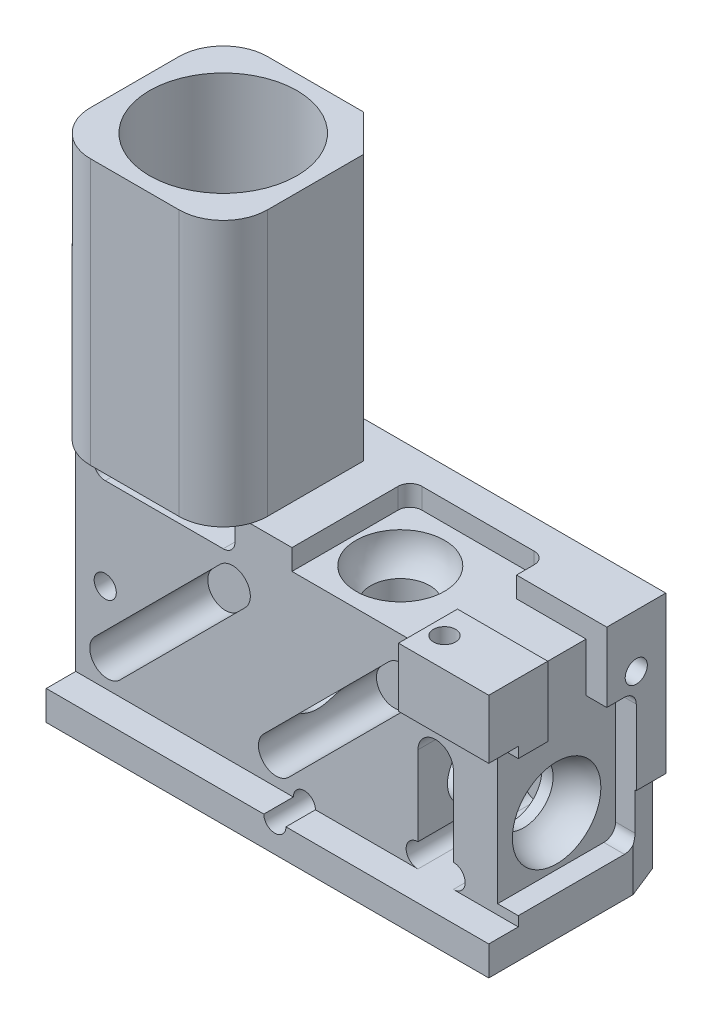
SolidWorks part; units mm, degrees
ref_plane "Front Plane" through (0, 0, 0) normal (0, 0, 1) x (1, 0, 0)
ref_plane "Top Plane" through (0, 0, 0) normal (0, 1, 0) x (1, 0, 0)
ref_plane "Right Plane" through (0, 0, 0) normal (1, 0, 0) x (0, 0, -1)
sketch "Sketch1" plane through (0, 0, 0) normal (0, 1, 0) x (1, 0, 0)
  line L1 (7.5, 3) -> (-7.5, 3)
  line L2 (7.5, 3) -> (7.5, -3)
  line L3 (7.5, -3) -> (-7.5, -3)
  line L4 (-7.5, 3) -> (-7.5, -3)
  line L5 (7.5, 3) -> (-7.5, -3) construction
  line L6 (7.5, -3) -> (-7.5, 3) construction
  point P0 (0, 0)
  dimension "D1" = 6
  dimension "D2" = 15
extrude "Main Body Ext" add sketch "Sketch1" along normal blind 8.3
sketch "Sketch8" plane through (0, 8.3, 0) normal (0, 1, 0) x (1, 0, 0)
  line L0 (-2.75, 3) -> (-1.5, 1.75)
  line L1 (-2.75, 3) -> (-7.5, 3)
  line L2 (-1.5, 1.75) -> (-1.5, -3)
  line L3 (-1.5, -3) -> (-7.5, -3)
  line L4 (-7.5, 3) -> (-7.5, -3)
  line L5 (-2.125, 2.375) -> (-7.5, -3) construction
  line L6 (-1.5, -3) -> (-7.5, 3) construction
  line L7 (-7.5, 3) -> (-7.5, -3) construction
  line L8 (0, 0) -> (-4.5, 0) construction
  point P0 (-4.5, 0)
  dimension "D1" = 6
  dimension "D2" = 6
  dimension "D3" = 1.25
  dimension "D4" = 3
extrude "Emission Path Ext" add sketch "Sketch8" along normal blind 9
sketch "Sketch3" plane through (0, 0, 0) normal (0, -1, 0) x (1, 0, 0)
  line L0 (-7.5, -3) -> (-7.5, 3) construction
  line L1 (0, 0) -> (-4.5, 0) construction
  circle A0 centre (-4.5, 0) radius 1.25
  dimension "D1" = 3
  dimension "D2" = 2.5
extrude "Emission and Grin Cut" cut sketch "Sketch3" against normal through all
sketch "Sketch4" plane through (7.5, 0, 0) normal (1, 0, 0) x (0, 0, -1)
  line L1 (-3, 0) -> (3, 0) construction
  circle A0 centre (0, 3) radius 1
  dimension "D1" = 2
  dimension "D2" = 3
extrude "Drum Lens Cut" cut sketch "Sketch4" against normal offset from surface (13 mm away) 2 up to face at (-7.5, 8.65, 0)
sketch "Sketch41" plane through (0, 8.3, 0) normal (0, 1, 0) x (1, 0, 0)
  line L1 (7.5, 3) -> (-2.75, 3) construction
  line L2 (-1.5, -3) -> (-1.5, 1.75) construction
  circle A0 centre (1.5, 0) radius 1
  dimension "D1" = 2
  dimension "D2" = 3
  dimension "D3" = 3
extrude "Addtl Light Source" cut sketch "Sketch41" against normal blind 5
sketch "Sketch5" plane through (0, 0, 3) normal (0, 0, 1) x (1, 0, 0)
  line L0 (-7.5, 0) -> (7.5, 0) construction
  line L1 (7.5, 8.3) -> (-7.5, 8.3)
  line L2 (7.5, 8.3) -> (7.5, 1)
  line L3 (7.5, 1) -> (-7.5, 1)
  line L4 (-7.5, 8.3) -> (-7.5, 1)
  line L5 (7.5, 8.3) -> (-7.5, 1) construction
  line L6 (7.5, 1) -> (-7.5, 8.3) construction
  line L7 (-1.5, 8.3) -> (7.5, 8.3) construction
  line L9 (7.5, 8.3) -> (7.5, 0) construction
  line L10 (-7.5, 17.3) -> (-7.5, 0) construction
  point P0 (0, 4.65)
  dimension "D1" = 1
extrude "FilterCover Cut1" cut sketch "Sketch5" against normal blind 1
sketch "Top-LED-Screw" plane through (0, 0, 2) normal (0, 0, 1) x (1, 0, 0)
  line L1 (7.5, 8.3) -> (4.44, 8.3)
  line L2 (7.5, 8.3) -> (7.5, 6.3)
  line L3 (7.5, 6.3) -> (4.44, 6.3)
  line L4 (4.44, 8.3) -> (4.44, 6.3)
  dimension "D1" = 2
  dimension "D2" = 3.06
extrude "Boss-Extrude1" add sketch "Top-LED-Screw" along normal blind 1
sketch "Sketch6" plane through (0, 0, 2) normal (0, 0, 1) x (1, 0, 0)
  line L0 (5.3, 4.5) -> (5.3, 1.8)
  line L1 (4.1, 4.5) -> (5.3, 4.5) construction
  line L2 (5.3, 1) -> (4.1, 1)
  line L3 (-7.5, 1) -> (7.5, 1) construction
  line L4 (-7.5, 8.3) -> (-7.5, 1) construction
  line L5 (-6.9, 7.9) -> (-6.9, 7.5)
  line L6 (4.1, 4.5) -> (4.1, 1.8)
  line L7 (-1.5, 8.3) -> (-7.5, 8.3) construction
  line L8 (-2.1, 7.9) -> (-2.1, 7.5)
  line L9 (-6, 1.5) -> (-6, 1) construction
  line L10 (-2.5, 8.3) -> (-6.5, 8.3)
  line L11 (-4.5, 3) -> (-4.5, 1) construction
  line L12 (-4.5, 3) -> (0.4851, 3) construction
  line L13 (-2.5, 7.1) -> (-6.5, 7.1)
  line L14 (-0.282, 1.5) -> (-0.282, 1) construction
  line L15 (-2.5, 8.3) -> (-6.5, 7.1) construction
  line L16 (-2.5, 7.1) -> (-6.5, 8.3) construction
  line L17 (4.1, 1.8) -> (5.3, 1.8) construction
  line L18 (-2.6059, 6.5912) -> (-6.8485, 2.3485)
  line L19 (7.5, 1) -> (7.5, 6.3) construction
  line L20 (-1.7574, 5.7426) -> (-6, 1.5)
  line L21 (-2.6059, 6.5912) -> (-6, 1.5) construction
  line L22 (-6.8485, 2.3485) -> (-1.7574, 5.7426) construction
  line L23 (1.826, 3.6081) -> (1.826, 1.6081) construction
  line L24 (1.826, 3.6081) -> (3.2165, 3.6081) construction
  line L25 (3.1121, 6.5912) -> (-1.1305, 2.3485)
  line L26 (3.9606, 5.7426) -> (-0.282, 1.5)
  line L27 (3.1121, 6.5912) -> (-0.282, 1.5) construction
  line L28 (-1.1305, 2.3485) -> (3.9606, 5.7426) construction
  line L33 (-2.5, 8.3) -> (1.102, 8.3) construction
  line L34 (1.102, 8.3) -> (1.102, 7.1) construction
  line L35 (1.102, 7.1) -> (-2.5, 7.1) construction
  line L36 (-6.5, 7.1) -> (-4.098, 7.1) construction
  line L37 (-4.098, 7.1) -> (-4.098, 8.3) construction
  line L38 (-4.098, 8.3) -> (-6.5, 8.3) construction
  line L39 (-6.5, 8.3) -> (-2.7284, 6.992) construction
  arc A0 (-2.5, 8.3) -> (-2.1, 7.9) centre (-2.5, 7.9) cw
  arc A1 (4.1, 4.5) -> (5.3, 4.5) centre (4.7, 4.5) cw
  arc A2 (-6.5, 8.3) -> (-6.9, 7.9) centre (-6.5, 7.9) ccw
  arc A3 (-2.6059, 6.5912) -> (-1.7574, 5.7426) centre (-2.1816, 6.1669) cw
  arc A4 (4.1, 1) -> (4.1, 1.8) centre (4.1, 1.4) cw
  arc A5 (-6.8485, 2.3485) -> (-6, 1.5) centre (-6.4243, 1.9243) ccw
  arc A6 (5.3, 1) -> (5.3, 1.8) centre (5.3, 1.4) ccw
  arc A7 (-6.5, 7.1) -> (-6.9, 7.5) centre (-6.5, 7.5) cw
  arc A8 (-2.5, 7.1) -> (-2.1, 7.5) centre (-2.5, 7.5) ccw
  arc A9 (3.1121, 6.5912) -> (3.9606, 5.7426) centre (3.5364, 6.1669) cw
  arc A10 (-1.1305, 2.3485) -> (-0.282, 1.5) centre (-0.7063, 1.9243) ccw
  point P5 (-4.5, 7.7)
  point P10 (-4.3029, 4.0456)
  point P21 (1.415, 4.0456)
  dimension "D10" = 0.5
  dimension "D5" = 2.2
  dimension "D8" = 0.4
  dimension "D11" = 0.4
  dimension "D12" = 0.4
  dimension "D1" = 1.2
  dimension "D2" = 45
  dimension "D3" = 3.5
  dimension "D4" = 1.2
  dimension "D6" = 2
  dimension "D7" = 4
  dimension "D9" = 3
  dimension "D13" = 1.2
  dimension "D14" = 3
  dimension "D15" = 6
  dimension "D16" = 45
  dimension "D17" = 0.5
  dimension "D18" = 1.2
  dimension "D19" = 2
  dimension "D20" = 6
extrude "FilterSet Cut2" cut sketch "Sketch6" against normal offset from surface (4 mm away) 1 up to face at (-0.0625, 9.2833, -3)
sketch "Sketch10" plane through (0, 17.3, 0) normal (0, 1, 0) x (1, 0, 0)
  line L0 (-4.5, 0) -> (-4.5, -3) construction
  line L1 (-7.5, -3) -> (-1.5, -3) construction
  line L3 (-4.5, 0) -> (-7.5, 0) construction
  line L4 (-7.5, 3) -> (-7.5, -3) construction
  circle A0 centre (-4.5, 0) radius 2.5
  dimension "D1" = 5
extrude "Emission Lens Cut" cut sketch "Sketch10" against normal offset from surface (8.5 mm away) 0.5 up to face at (-4.125, 8.3, 1.3125)
sketch "Sketch12" plane through (7.5, 0, 0) normal (1, 0, 0) x (0, 0, -1)
  line L0 (0, 3.635) -> (0, 0) construction
  line L1 (1.6, 5.94) -> (-1.6, 5.94)
  line L2 (1.6, 5.94) -> (1.6, 1.33) construction
  line L3 (-2, 1.33) -> (1.6, 1.33)
  line L4 (-1.6, 5.94) -> (-1.6, 1.33) construction
  line L5 (1.6, 5.94) -> (-1.6, 1.33) construction
  line L6 (1.6, 1.33) -> (-1.6, 5.94) construction
  line L7 (-3, 0) -> (3, 0) construction
  line L9 (-1.6, 5.94) -> (-2, 5.94)
  line L10 (-2, 1) -> (-2, 6.3) construction
  line L11 (-2, 5.94) -> (-2, 1.33)
  line L12 (2, 5.54) -> (2, 1.73)
  arc A1 (1.6, 5.94) -> (2, 5.54) centre (1.6, 5.54) cw
  arc A2 (1.6, 1.33) -> (2, 1.73) centre (1.6, 1.73) ccw
  circle A3 centre (0, 3) radius 1 construction
  point P0 (0, 3.635)
  dimension "D2" = 4.61
  dimension "D3" = 1.67
  dimension "D1" = 3.2
  dimension "D4" = 0.4
sketch "Sketch15" plane through (0, 0, 0) normal (0, -1, 0) x (1, 0, 0)
  line L0 (-6.25, 1.875) -> (-6.25, -1.875) construction
  line L2 (-1.5, 0) -> (-4.5, 0) construction
  line L3 (-4.5, 0) -> (-6.25, 0) construction
  circle A0 centre (-6.25, -1.875) radius 0.795
  circle A1 centre (-6.25, 1.875) radius 0.795
  circle A2 centre (-1.5, 0) radius 0.795
  dimension "D4" = 1.59
  dimension "D1" = 3.75
  dimension "D2" = 3
  dimension "D3" = 1.75
extrude "Magnets Cut" cut sketch "Sketch15" against normal blind 0.9
sketch "Sketch18" plane through (0, 0, 2) normal (0, 0, 1) x (1, 0, 0)
  line L0 (-7.5, 8.3) -> (-7.5, 1) construction
  line L1 (7.5, 1) -> (7.5, 6.3) construction
  line L2 (4.44, 8.3) -> (-1.5, 8.3) construction
  line L3 (-7.5, 0) -> (7.5, 0) construction
  line L7 (-7.5, 1) -> (4.1, 1) construction
  line L9 (-7.5, 1) -> (-7.5, 0) construction
  circle A0 centre (-6.5, 4) radius 0.375
  circle A1 centre (6, 5.8) radius 0.375
  circle A2 centre (0.25, 1) radius 0.375
  dimension "D1" = 0.75
  dimension "D2" = 1
  dimension "D3" = 2.5
  dimension "D4" = 1.5
  dimension "D5" = 3
  dimension "D6" = 1
  dimension "D7" = 7.75
extrude "Screw Holes Cut" cut sketch "Sketch18" against normal blind 2.5 and the other way through all
fillet "External Fillet 1" radius 1.5 2 edges at (-7.5, 8.65, -3)
sketch "Sketch14" plane through (0, 0, 0) normal (0, -1, 0) x (1, 0, 0)
  line L0 (7.5, -3) -> (7.5, -1.8916)
  line L1 (7.5, 3) -> (7.5, -3) construction
  line L2 (7.5, -1.8916) -> (7.0566, -3)
  line L3 (7.5, -3) -> (-6, -3) construction
  line L4 (7.0566, -3) -> (7.5, -3)
  line L5 (7.5, -3) -> (-7.5, 3) construction
  line L6 (-7.5, -1.5) -> (-7.5, 3) construction
  line L7 (-7.5, 3) -> (7.5, 3) construction
  dimension "D1" = 1.1938
sketch "Sketch28" plane through (0, 7.1, 0) normal (0, 1, 0) x (1, 0, 0)
  circle A0 centre (-4.5, 0) radius 1.5
  dimension "D1" = 3
extrude "Vertical-Path-Cut" cut sketch "Sketch28" against normal blind 4 and the other way through all
extrude "Set-Screw-Notch" cut sketch "Sketch14" against normal blind 3
extrude "Cut-Extrude Original Light" cut sketch "Sketch12" against normal blind 0.7
sketch "Sketch44" plane through (0, 8.3, 0) normal (0, 1, 0) x (1, 0, 0)
  line L0 (-0.17, -2) -> (4.44, -2)
  line L1 (-0.17, -2) -> (-0.17, 1.6)
  line L2 (4.44, -2) -> (4.44, 1.6)
  line L3 (0.23, 2) -> (4.04, 2)
  line L6 (4.44, -2) -> (-1.5858, -2) construction
  circle A0 centre (1.5, 0) radius 1 construction
  arc A1 (4.44, 1.6) -> (4.04, 2) centre (4.04, 1.6) ccw
  arc A2 (-0.17, 1.6) -> (0.23, 2) centre (0.23, 1.6) cw
  point P10 (4.44, 2)
  point P13 (-0.17, 2)
  dimension "D3" = 1.67
  dimension "D4" = 0.4
  dimension "D5" = 0.4
  dimension "D1" = 4
  dimension "D2" = 4.61
extrude "Cut-Extrude Addtl Light" cut sketch "Sketch44" against normal blind 0.7
sketch "Sketch29" plane through (7.5, 0, 0) normal (1, 0, 0) x (0, 0, -1)
  line L0 (3, 8.3) -> (3, 3) construction
  line L1 (-3, 8.3) -> (3, 8.3) construction
  circle A0 centre (2, 6.5) radius 0.375
  circle A1 centre (0, 3) radius 1 construction
  dimension "D1" = 0.75
  dimension "D2" = 1
  dimension "D3" = 1.8
  dimension "D5" = 3.5
  dimension "D6" = 2
extrude "Side-LED-Screw" cut sketch "Sketch29" against normal blind 2.5
sketch "Sketch31" plane through (6.8, 0, 0) normal (1, 0, 0) x (0, 0, -1)
  circle A0 centre (0, 3) radius 1.6
  dimension "D1" = 3.2
sketch "Sketch32" plane through (7.5, 0, 0) normal (1, 0, 0) x (0, 0, -1)
  line L0 (-3, 8.3) -> (3, 8.3) construction
  line L1 (-1, 8.3) -> (1, 8.3)
  line L2 (-1, 8.3) -> (-1, 5.94)
  line L3 (-1, 5.94) -> (1, 5.94)
  line L4 (1, 8.3) -> (1, 5.94)
  line L5 (1.6, 5.94) -> (-2, 5.94) construction
  line L6 (-2, 5.94) -> (-2, 6.3) construction
  line L8 (3, 8.3) -> (3, 3) construction
  dimension "D1" = 1
  dimension "D2" = 2
extrude "Side-Wire-Slot-Cut" cut sketch "Sketch32" against normal up to surface (0.7 mm away) up to face at (6.8, 3.635, -0.5609)
sketch "Sketch45" plane through (0, 8.3, 0) normal (0, 1, 0) x (1, 0, 0)
  line L1 (4.44, -1) -> (6.8, -1)
  line L2 (4.44, -1) -> (4.44, 1)
  line L3 (4.44, 1) -> (6.8, 1)
  line L4 (6.8, -1) -> (6.8, 1)
  line L5 (4.44, -1) -> (6.8, 1) construction
  line L6 (4.44, 1) -> (6.8, -1) construction
  line L7 (6.8, 1) -> (6.8, -1) construction
  line L8 (4.44, -3) -> (4.44, 1.6) construction
  line L12 (6.8, -1) -> (7.5, -1) construction
  line L13 (6.8, 1) -> (7.5, 1) construction
extrude "Top-LED-slot" cut sketch "Sketch45" against normal blind 0.7
sketch "Sketch33" plane through (0, 0, 0) normal (0, 0, 1) x (1, 0, 0)
  line L0 (6.8, 3) -> (5.3, 3)
  line L1 (6.8, 1.4) -> (6.8, 4.6) construction
  line L2 (6.8, 3) -> (6.8, 4.5)
  arc A0 (5.3, 3) -> (6.8, 4.5) centre (6.8, 3) cw
  dimension "D2" = 1.5
revolve "Side-BallLens_Cut" cut sketch "Sketch33" angle 360 about L0
sketch "Sketch46" plane through (0, 7.6, 0) normal (0, 1, 0) x (1, 0, 0)
  circle A0 centre (1.5, 0) radius 1.5 construction
ref_plane "Plane1" through (1.5, 0, 0) normal (1, 0, 0) x (0, 0, -1)
sketch "Sketch47" plane through (1.5, 0, 0) normal (1, 0, 0) x (0, 0, -1)
  line L4 (-1.5, 7.6) -> (0, 7.6)
  line L5 (0, 7.6) -> (0, 6.1373)
  line L6 (1, 7.6) -> (-1, 7.6) construction
  arc A0 (0, 6.1373) -> (-1.5, 7.6) centre (0, 7.6378) cw
revolve "Top-BallLens_Cut" cut sketch "Sketch47" angle 360 about L5
sketch "Sketch36" plane through (0, 17.3, 0) normal (0, 1, 0) x (1, 0, 0)
  line L0 (-7.5, -1.5) -> (-7.5, -3)
  line L1 (-7.5, 1.5) -> (-7.5, -3) construction
  line L2 (-7.5, -3) -> (-6, -3)
  line L3 (-7.5, -3) -> (-3, -3) construction
  arc A0 (-7.5, -1.5) -> (-6, -3) centre (-6, -1.5) ccw
  dimension "D1" = 1.5
  dimension "D2" = 1.5
extrude "Cut-Extrude16" cut sketch "Sketch36" against normal up to surface (9 mm away)
sketch "Sketch37" plane through (0, 8.8, 0) normal (0, 1, 0) x (1, 0, 0)
  circle A0 centre (-4.5, 0) radius 2
  circle A1 centre (-4.5, 0) radius 1.5 construction
  dimension "D1" = 4
extrude "Cut-Extrude17" cut sketch "Sketch37" against normal up to next
sketch "Sketch48" plane through (0, 0, 0) normal (0, -1, 0) x (1, 0, 0)
  line L0 (7.0566, -3) -> (-6, -3) construction
  line L1 (-7.5, -1.5) -> (-7.5, 3) construction
  circle A0 centre (-2, -2) radius 0.5
  dimension "D1" = 1
  dimension "D2" = 5.5
  dimension "D3" = 1
extrude "Peg-extrude" cut sketch "Sketch48" against normal blind 2
sketch "Sketch51" plane through (0, 8.3, 0) normal (0, 1, 0) x (1, 0, 0)
  circle A0 centre (5, -2) radius 0.375
  circle A1 centre (1.5, 0) radius 1.5 construction
  dimension "D1" = 0.75
  dimension "D2" = 3.5
  dimension "D3" = 2
extrude "Top-LE-Screw" cut sketch "Sketch51" against normal blind 2.1
